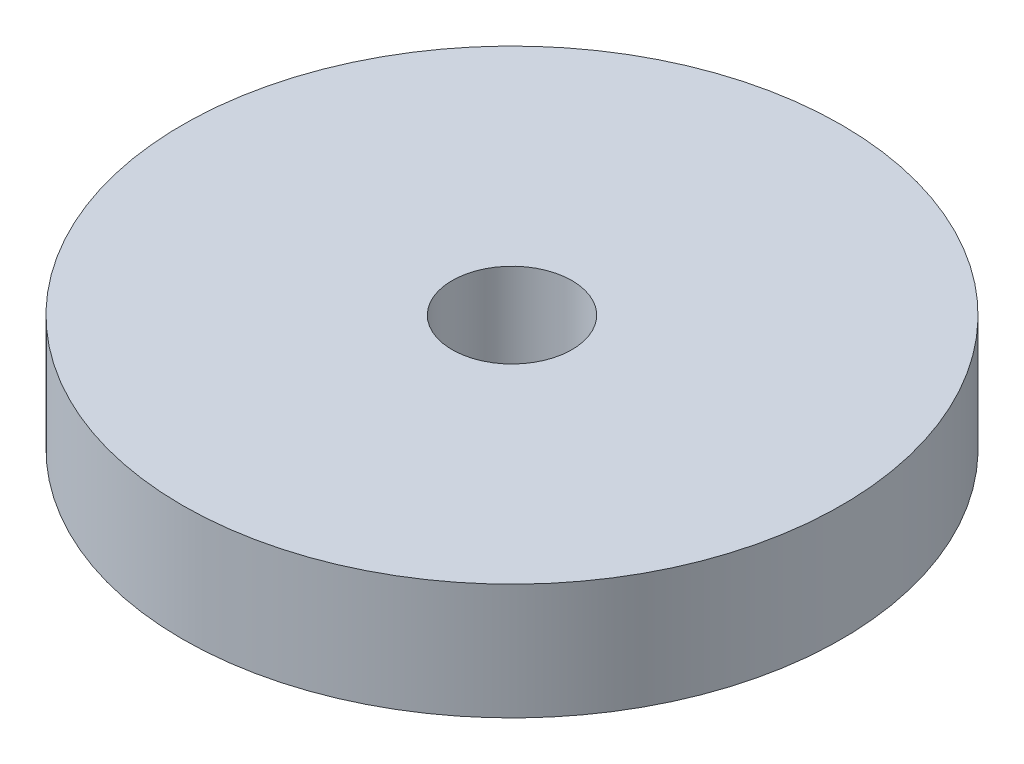
SolidWorks part; units mm, degrees
ref_plane "Front Plane" through (0, 0, 0) normal (0, 0, 1) x (1, 0, 0)
ref_plane "Top Plane" through (0, 0, 0) normal (0, 1, 0) x (1, 0, 0)
ref_plane "Right Plane" through (0, 0, 0) normal (1, 0, 0) x (0, 0, -1)
sketch "Sketch1" plane through (0, 0, 0) normal (0, 1, 0) x (1, 0, 0)
  circle A0 centre (0, 0) radius 82.5
  dimension "FLANGE_OD" = 165
extrude "Boss-Extrude1" add sketch "Sketch1" along normal blind 29
sketch "Sketch2" plane through (0, 0, 0) normal (0, 1, 0) x (1, 0, 0)
  circle A0 centre (0, 0) radius 15
  dimension "BORE_D" = 30
extrude "Cut-Extrude1" cut sketch "Sketch2" along normal through all
sketch "Sketch3" plane through (0, 29, 0) normal (0, 1, 0) x (1, 0, 0)
  circle A0 centre (0, 0) radius 12.0004 construction
  circle A1 centre (-12.0004, 0) radius 2.6921
  dimension "BOLT_D" = 5.3842
  dimension "BOLT_PCD" = 24.0007
extrude "Cut-Extrude2" cut sketch "Sketch3" against normal blind 22.2747 rebuild error yes
pattern_circular "CirPattern1" count 6 over 360 rebuild error yes
